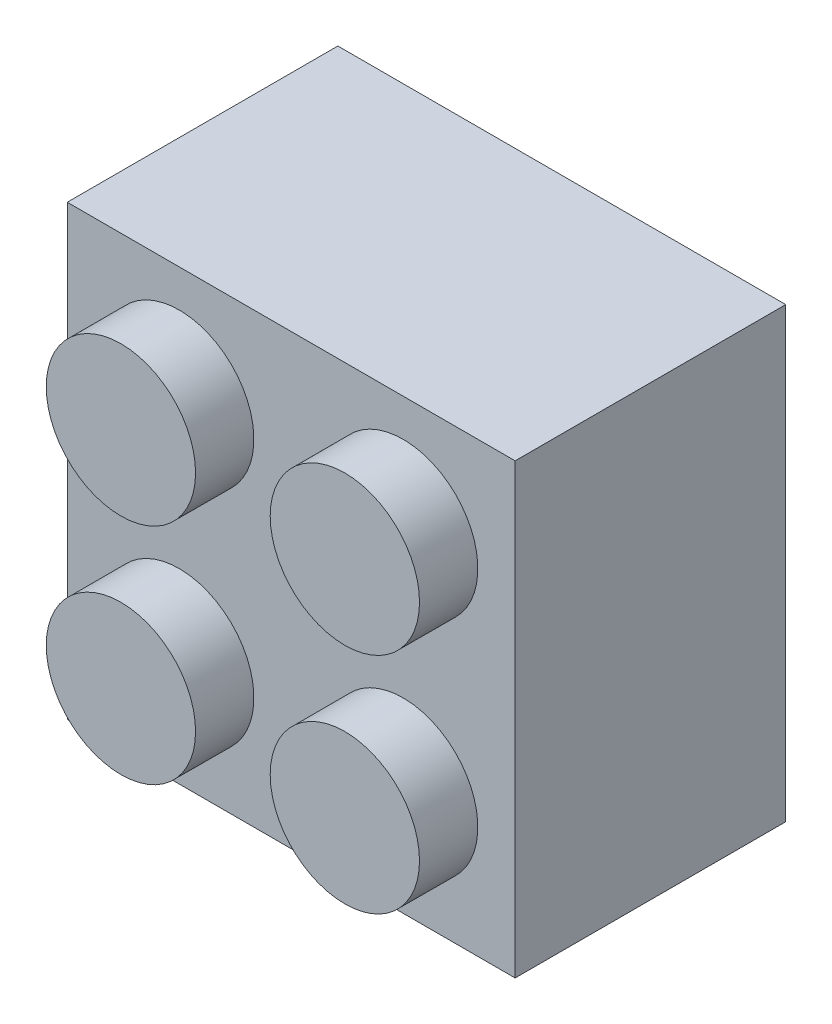
SolidWorks part; units mm, degrees
ref_plane "Plan de face" through (0, 0, 0) normal (0, 0, 1) x (1, 0, 0)
ref_plane "Plan de dessus" through (0, 0, 0) normal (0, 1, 0) x (1, 0, 0)
ref_plane "Plan de droite" through (0, 0, 0) normal (1, 0, 0) x (0, 0, -1)
sketch "Esquisse1" plane through (0, 0, 0) normal (0, 0, 1) x (1, 0, 0)
  line L0 (0, 59.0841) -> (0, -56.3445) construction
  line L1 (-61.915, 0) -> (66.2984, 0) construction
  line L2 (-48, 48) -> (48, 48)
  line L3 (48, 48) -> (48, -48)
  line L4 (48, -48) -> (-48, -48)
  line L5 (-48, -48) -> (-48, 48)
  line L6 (-40, 40) -> (40, 40)
  line L7 (40, 40) -> (40, -40)
  line L8 (40, -40) -> (-40, -40)
  line L9 (-40, -40) -> (-40, 40)
  point P9 (0, -56.3445)
  point P10 (0, 0)
  point P11 (0, 0)
  point P12 (0, 0)
  point P13 (0, 0)
  point P14 (0, 0)
  point P15 (0, 0)
  point P16 (0, 0)
  point P17 (0, 59.0841)
  point P18 (0, 0)
  point P19 (-61.915, 0)
  point P20 (0, 0)
  point P21 (66.2984, 0)
  dimension "D1" = 96
  dimension "D2" = 8
extrude "Boss.-Extru.1" add sketch "Esquisse1" along normal blind 48
sketch "Esquisse2" plane through (0, 0, 48) normal (0, 0, 1) x (1, 0, 0)
  line L1 (-48, 48) -> (48, 48)
  line L2 (-48, 48) -> (-48, -48)
  line L3 (-48, -48) -> (48, -48)
  line L4 (48, 48) -> (48, -48)
extrude "Boss.-Extru.3" add sketch "Esquisse2" along normal offset from surface (10 mm away) 58 up to face at (0, 0, 0)
sketch "Esquisse3" plane through (0, 0, 58) normal (0, 0, 1) x (1, 0, 0)
  line L0 (-48, -48) -> (48, 48) construction
  line L1 (48, -48) -> (-48, 48) construction
  line L2 (-24, 40) -> (24, 40) construction
  line L3 (-48, 48) -> (48, 48) construction
  circle A0 centre (-24, 24) radius 16
  circle A1 centre (24, 24) radius 16
  circle A2 centre (24, -24) radius 16
  circle A3 centre (-24, -24) radius 16
  point P19 (0, 0)
  point P21 (0, 0)
  dimension "D1" = 32
  dimension "D3" = 8
  dimension "D2" = 4
extrude "Boss.-Extru.4" add sketch "Esquisse3" along normal blind 12.5
sketch "Esquisse4" plane through (0, 0, 0) normal (0, 0, -1) x (-1, 0, 0)
  circle A0 centre (0, 0) radius 18.5
  circle A1 centre (0, 0) radius 11.5
  point P4 (0, 0)
  dimension "D1" = 37
  dimension "D2" = 23
extrude "Boss.-Extru.5" add sketch "Esquisse4" against normal up to surface (48 mm away) up to face at (0, 0, 48)
chamfer "Chanfrein1" distance 48 angle 5 1 edges at (18.5, 0, 48) first distance on face at (-18.5, 0, 0)
